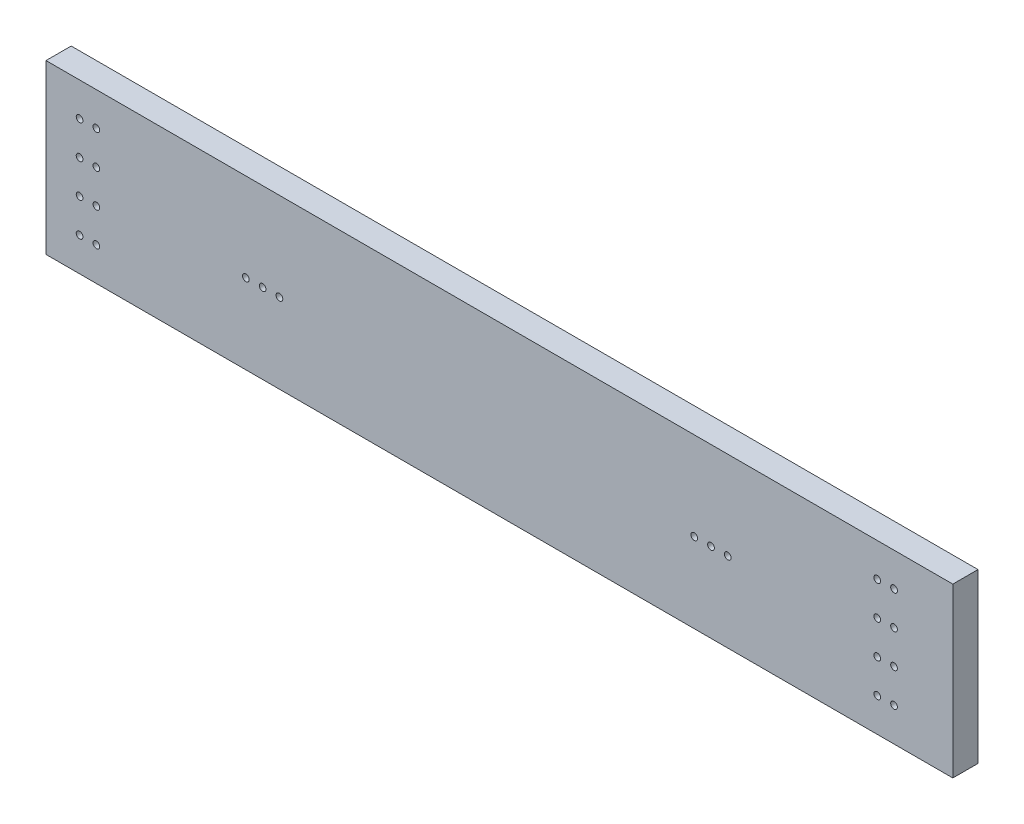
SolidWorks part; units mm, degrees
material "Pine"
ref_plane "Front Plane" through (0, 0, 0) normal (0, 0, 1) x (1, 0, 0)
ref_plane "Top Plane" through (0, 0, 0) normal (0, 1, 0) x (1, 0, 0)
ref_plane "Right Plane" through (0, 0, 0) normal (1, 0, 0) x (0, 0, -1)
sketch "Sketch1" plane through (0, 0, 0) normal (0, 0, 1) x (1, 0, 0)
  line L1 (-342.9, -63.5) -> (342.9, -63.5)
  line L2 (-342.9, -63.5) -> (-342.9, 63.5)
  line L3 (-342.9, 63.5) -> (342.9, 63.5)
  line L4 (342.9, -63.5) -> (342.9, 63.5)
  line L5 (-342.9, -63.5) -> (342.9, 63.5) construction
  line L6 (-342.9, 63.5) -> (342.9, -63.5) construction
  point P0 (0, 0)
  dimension "D1" = 685.8
  dimension "D2" = 127
extrude "Boss-Extrude1" add sketch "Sketch1" along normal blind 19.05
sketch "Sketch2" plane through (0, 0, 19.05) normal (0, 0, 1) x (1, 0, 0)
  line L0 (342.9, -63.5) -> (342.9, 63.5) construction
  line L1 (342.9, 63.5) -> (-342.9, 63.5) construction
  line L3 (-342.9, 63.5) -> (-342.9, -63.5) construction
  line L4 (-342.9, 63.5) -> (342.9, 63.5) construction
  circle A1 centre (298.45, 38.1) radius 2.54
  circle A2 centre (298.45, 12.7) radius 2.54
  circle A3 centre (298.45, -12.7) radius 2.54
  circle A4 centre (298.45, -38.1) radius 2.54
  circle A5 centre (285.75, -38.1) radius 2.54
  circle A6 centre (285.75, -12.7) radius 2.54
  circle A7 centre (285.75, 12.7) radius 2.54
  circle A8 centre (285.75, 38.1) radius 2.54
  circle A9 centre (-317.5, 38.1) radius 2.54
  circle A10 centre (-304.8, 38.1) radius 2.54
  circle A11 centre (-317.5, 12.7) radius 2.54
  circle A12 centre (-304.8, 12.7) radius 2.54
  circle A13 centre (-317.5, -12.7) radius 2.54
  circle A14 centre (-304.8, -12.7) radius 2.54
  circle A15 centre (-317.5, -38.1) radius 2.54
  circle A16 centre (-304.8, -38.1) radius 2.54
  circle A17 centre (147.32, -3.175) radius 2.54
  circle A18 centre (160.02, -3.175) radius 2.54
  circle A19 centre (172.72, -3.175) radius 2.54
  circle A20 centre (-191.77, -3.175) radius 2.54
  circle A21 centre (-179.07, -3.175) radius 2.54
  circle A22 centre (-166.37, -3.175) radius 2.54
  point P56 (0, 0)
  point P57 (0, 0)
  dimension "D1" = 5.08
  dimension "D8" = 5.08
  dimension "D15" = 5.08
  dimension "D21" = 5.08
  dimension "D2" = 44.45
  dimension "D3" = 12.7
  dimension "D4" = 25.4
  dimension "D5" = 25.4
  dimension "D6" = 25.4
  dimension "D7" = 25.4
  dimension "D9" = 25.4
  dimension "D10" = 25.4
  dimension "D11" = 25.4
  dimension "D12" = 25.4
  dimension "D13" = 25.4
  dimension "D14" = 12.7
  dimension "D16" = 12.7
  dimension "D17" = 12.7
  dimension "D18" = 147.32
  dimension "D19" = 66.675
  dimension "D20" = 66.675
  dimension "D22" = 12.7
  dimension "D23" = 12.7
  dimension "D24" = 166.37
extrude "Cut-Extrude1" cut sketch "Sketch2" against normal through all
